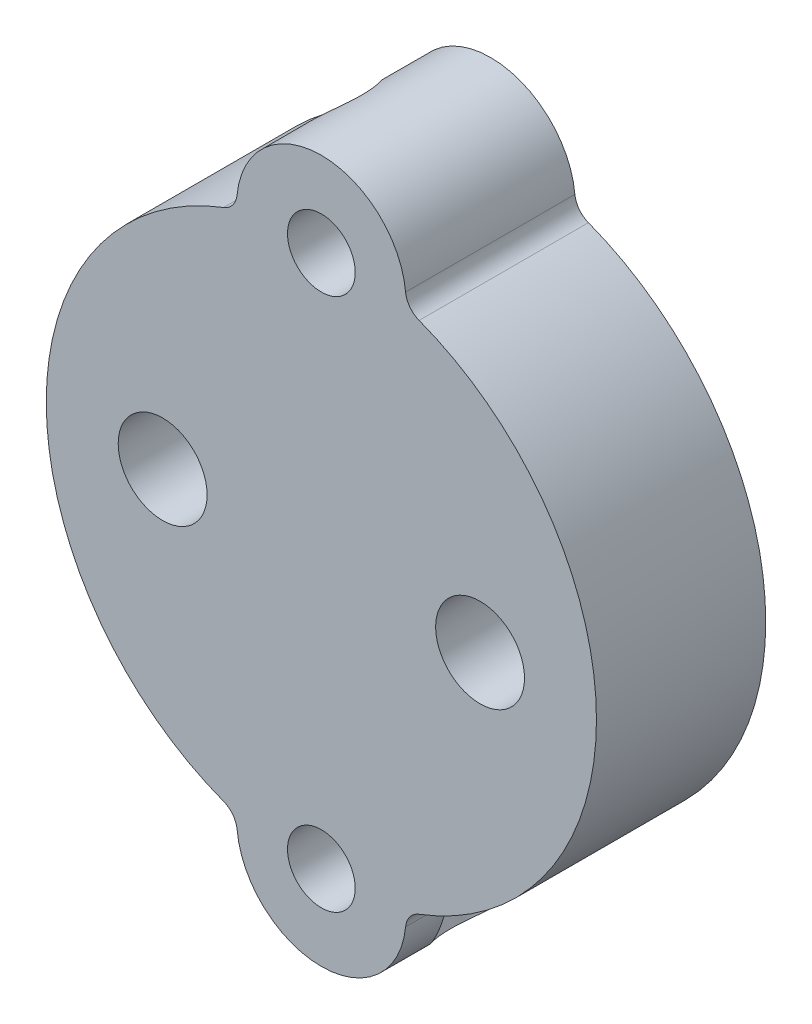
SolidWorks part; units mm, degrees
ref_plane "Front Plane" through (0, 0, 0) normal (0, 0, 1) x (1, 0, 0)
ref_plane "Top Plane" through (0, 0, 0) normal (0, 1, 0) x (1, 0, 0)
ref_plane "Right Plane" through (0, 0, 0) normal (1, 0, 0) x (0, 0, -1)
sketch "Sketch1" plane through (0, 0, 0) normal (0, 0, 1) x (1, 0, 0)
  line L0 (0, 12.6) -> (0, -12.6) construction
  line L1 (-7.5, 0) -> (7.5, 0) construction
  arc A2 (4.6209, -12.151) -> (4.6209, 12.151) centre (0, 0) ccw
  circle A4 centre (0, 12.6) radius 1.6
  circle A5 centre (0, -12.6) radius 1.6
  circle A6 centre (7.5, 0) radius 2.1
  circle A7 centre (-7.5, 0) radius 2.1
  arc A42 (-3.9811, -12.9886) -> (3.9811, -12.9886) centre (0, -12.6) ccw
  arc A44 (-4.6209, 12.151) -> (-4.6209, -12.151) centre (0, 0) ccw
  arc A46 (3.9811, 12.9886) -> (-3.9811, 12.9886) centre (0, 12.6) ccw
  arc A150 (-3.9811, -12.9886) -> (-4.6209, -12.151) centre (-4.9764, -13.0857) ccw
  arc A152 (-4.6209, 12.151) -> (-3.9811, 12.9886) centre (-4.9764, 13.0857) ccw
  arc A154 (3.9811, 12.9886) -> (4.6209, 12.151) centre (4.9764, 13.0857) ccw
  arc A156 (4.6209, -12.151) -> (3.9811, -12.9886) centre (4.9764, -13.0857) ccw
  point P11 (0, 0)
  dimension "D3" = 4.2
  dimension "D4" = 3.2
  dimension "D5" = 4
  dimension "D1" = 13
  dimension "D6" = 1
  dimension "D2" = 15
  dimension "D7" = 3.9811
extrude "Boss-Extrude1" add sketch "Sketch1" along normal blind 8
ref_axis "Axis1" through (0, 0, -0.4) along (0, 0, 1)
ref_plane "Plane2" through (0, 0, 0) normal (-0.2588, 0.9659, 0) x (0, 0, 1)
sketch "Sketch3" plane through (0, 0, 0) normal (-0.2588, 0.9659, 0) x (0, 0, 1)
  line L0 (8, 13) -> (0, 13) construction
  circle A0 centre (4, 0) radius 2.1
  point P2 (0, 0)
  point P4 (4, 13)
  dimension "D1" = 4.2
extrude "Cut-Extrude1" cut sketch "Sketch3" against normal through all both and the other way through all
sketch "Sketch4" plane through (0, 0, 0) normal (0, 0, -1) x (-1, 0, 0)
  circle A0 centre (-7.5, 0) radius 3.4
  circle A1 centre (7.5, 0) radius 3.4
  circle A2 centre (7.5, 0) radius 2.1 construction
  point P7 (0, 0)
  dimension "D1" = 6.8
extrude "Cut-Extrude2" cut sketch "Sketch4" against normal blind 3 and the other way through all
